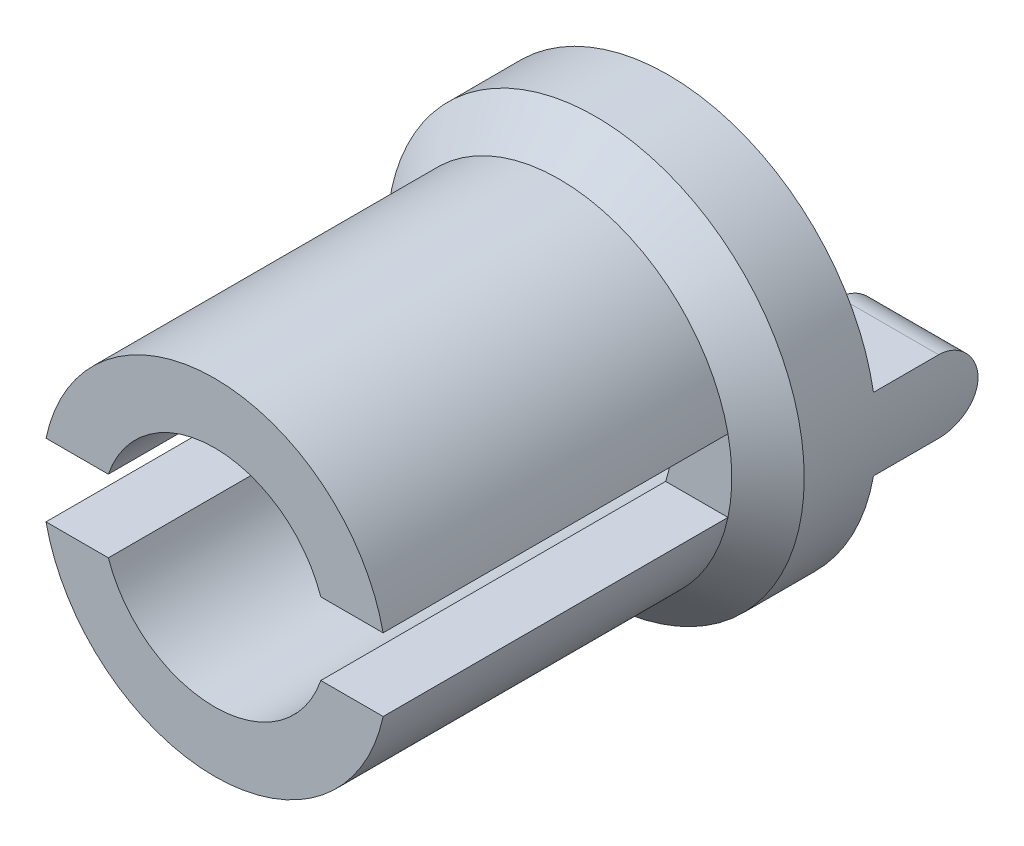
SolidWorks part; units mm, degrees
ref_plane "Front Plane" through (0, 0, 0) normal (0, 0, 1) x (1, 0, 0)
ref_plane "Top Plane" through (0, 0, 0) normal (0, 1, 0) x (1, 0, 0)
ref_plane "Right Plane" through (0, 0, 0) normal (1, 0, 0) x (0, 0, -1)
sketch "Sketch1" plane through (0, 0, 0) normal (0, 0, 1) x (1, 0, 0)
  line L0 (5.6751, -1) -> (2.9343, -1)
  line L1 (5.6751, 1) -> (2.9343, 1)
  line L2 (-2.9343, -1) -> (-5.6751, -1)
  line L3 (-2.9343, 1) -> (-5.6751, 1)
  line L4 (3.9443, -1) -> (3.9443, 1)
  circle A0 centre (0, 0) radius 3.1
  circle A2 centre (0, 0) radius 4.7625
  circle A3 centre (0, 0) radius 5.7625
  point P15 (4.7625, 0)
  point P16 (3.9443, 0)
  point P17 (0, 0)
  point P18 (0, 0)
  point P19 (0, 0)
  point P20 (0, 0)
  point P21 (0, 0)
  dimension "D1" = 6.2
  dimension "D3" = 9.525
  dimension "D4" = 2
  dimension "D2" = 1
extrude "Boss-Extrude1" add sketch "Sketch1" along normal blind 3 contours L1 A2 L3 A0 | L2 A2 L0 A0 | L3 A2 L2 A0 | A0 L0 L4 L1 | L0 A2 L1 L4 | A3 A2 | L0 A3 L1 A2 | L2 A3 L0 A2 | L3 A3 L2 A2 region at (4.3003, -1.1004, 0) region at (4.3364, 0, 0) region at (3.4935, 0, 0) region at (5.2302, 0, 0) region at (5.1657, -1.1231, 0) region at (3.4393, 1.1004, 0) region at (-3.8859, 0, 0) region at (-5.2302, 0, 0) region at (0, 4.8856, 0)
extrude "Boss-Extrude2" add sketch "Sketch1<9>" along normal offset from surface (12.525 mm away) 9.525 contours L2 A2 L0 A0 | L1 A2 L3 A0 region at (4.3003, -1.1004, 0) region at (3.4393, 1.1004, 0) up to face at (5.7625, 0, 3) offset beyond the face yes
sketch "Sketch1<9>" plane through (0, 0, 0) normal (0, 0, 1) x (1, 0, 0) same geometry as "Sketch1"
extrude "Boss-Extrude3" add sketch "Sketch1<10>" against normal blind 2.8 contours A0 L0 L4 L1 | L0 A2 L1 L4 | L3 A2 L2 A0 | L0 A3 L1 A2 | L3 A3 L2 A2 region at (4.3364, 0, 0) region at (3.4935, 0, 0) region at (5.2302, 0, 0) region at (-3.8859, 0, 0) region at (-5.2302, 0, 0)
sketch "Sketch1<10>" plane through (0, 0, 0) normal (0, 0, 1) x (1, 0, 0) same geometry as "Sketch1"
fillet "Fillet1" radius 1 4 edges at (-4.3047, -1, -2.8) (-4.3047, 1, -2.8) (4.3047, 1, -2.8) (4.3047, -1, -2.8)
chamfer "Chamfer1" distance 1 angle 45 1 edges at (5.7625, 0, 3)
equation "\"shaft_dia\"=6.2"
equation "\"D1@Sketch1\"=\"shaft_dia\""
equation "\"collar_id_.375in\"=9.525"
equation "\"D3@Sketch1\"=\"collar_id_.375in\""
equation "\"groove_depth\"=2.8"
equation "\"D2@Boss-Extrude1\"=\"groove_depth\""
equation "\"D1@Boss-Extrude3\"=\"groove_depth\""
